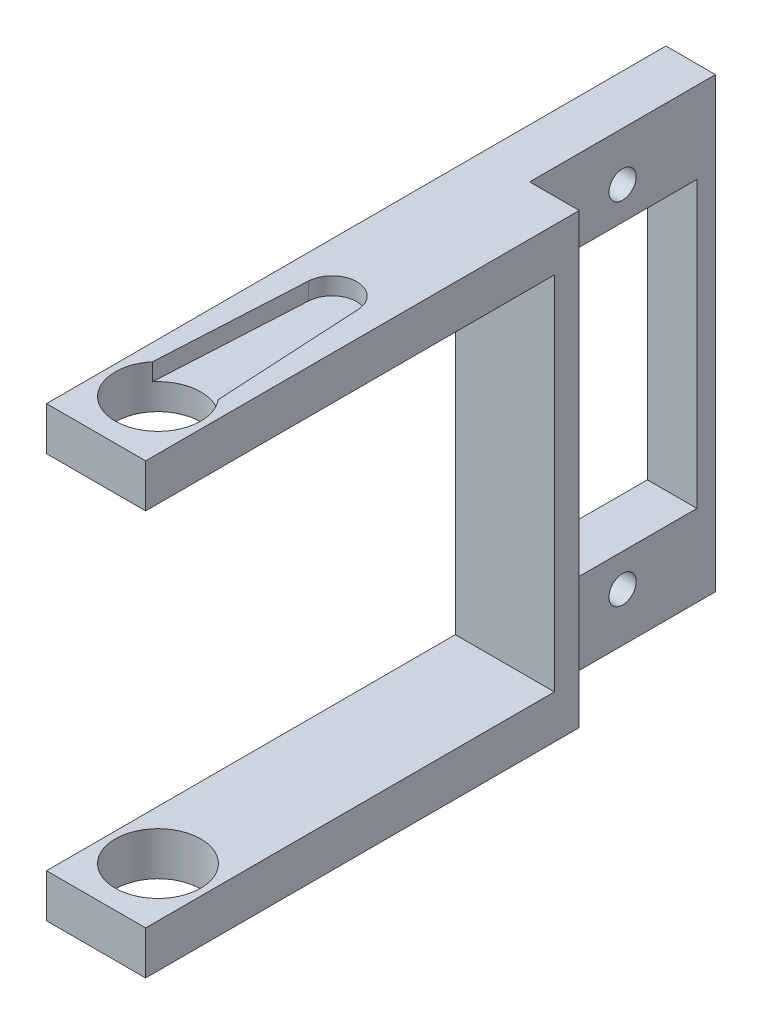
SolidWorks part; units mm, degrees
ref_plane "Front Plane" through (0, 0, 0) normal (0, 0, 1) x (1, 0, 0)
ref_plane "Top Plane" through (0, 0, 0) normal (0, 1, 0) x (1, 0, 0)
ref_plane "Right Plane" through (0, 0, 0) normal (1, 0, 0) x (0, 0, -1)
sketch "Sketch2" plane through (0, 0, 0) normal (0, 0, 1) x (1, 0, 0)
  line L1 (-8.6815, 1.0365) -> (-0.6815, 1.0365)
  line L2 (-8.6815, 1.0365) -> (-8.6815, -35.1135)
  line L3 (-8.6815, -35.1135) -> (-0.6815, -35.1135)
  line L4 (-0.6815, 1.0365) -> (-0.6815, -35.1135)
  line L13 (-8.6815, 1.0365) -> (-0.6815, 1.0365)
  line L14 (-8.6815, 1.0365) -> (-8.6815, -2.4635)
  line L15 (-8.6815, -2.4635) -> (-0.6815, -2.4635)
  line L16 (-0.6815, 1.0365) -> (-0.6815, -2.4635)
  line L21 (-8.6815, -35.1135) -> (-0.6815, -35.1135)
  line L22 (-8.6815, -35.1135) -> (-8.6815, -31.6135)
  line L23 (-8.6815, -31.6135) -> (-0.6815, -31.6135)
  line L24 (-0.6815, -35.1135) -> (-0.6815, -31.6135)
  dimension "D1" = 8
  dimension "D2" = 36.15
  dimension "D3" = 3.5
  dimension "D4" = 3.5
extrude "Boss-Extrude2" add sketch "Sketch2" along normal blind 35 contours L2 L15 L4 L1 | L22 L21 L24 L23 region at (-4.6815, -0.7135, 0)
extrude "Boss-Extrude3" add sketch "Sketch2<3>" along normal blind 2 contours L15 L2 L3 L4 region at (-4.6815, -17.0385, 0)
sketch "Sketch2<3>" plane through (0, 0, 0) normal (0, 0, 1) x (1, 0, 0) same geometry as "Sketch2"
sketch "Sketch7" plane through (0, 0, 0) normal (0, 0, -1) x (-1, 0, 0)
  line L5 (8.6815, -35.1135) -> (0.6815, -35.1135) construction
  line L6 (8.6815, 1.0365) -> (4.6815, 1.0365)
  line L7 (8.6815, 1.0365) -> (8.6815, -35.1135)
  line L8 (8.6815, -35.1135) -> (4.6815, -35.1135)
  line L9 (4.6815, 1.0365) -> (4.6815, -35.1135)
extrude "Boss-Extrude4" add sketch "Sketch7" along normal blind 15
sketch "Sketch8" plane through (-4.6815, 0, 0) normal (1, 0, 0) x (0, 0, -1)
  line L0 (7.5, -5.5385) -> (7.5, 1.0365) construction
  line L1 (1.5, -5.5385) -> (13.5, -5.5385)
  line L2 (1.5, -5.5385) -> (1.5, -28.5385)
  line L3 (1.5, -28.5385) -> (13.5, -28.5385)
  line L4 (13.5, -5.5385) -> (13.5, -28.5385)
  line L5 (15, 1.0365) -> (0, 1.0365) construction
  line L6 (13.5, -17.0385) -> (15, -17.0385) construction
  line L7 (15, 1.0365) -> (15, -35.1135) construction
  circle A2 centre (7.5, -2.8885) radius 1.1
  circle A3 centre (7.5, -31.1885) radius 1.1
  dimension "D3" = 2.2
  dimension "D1" = 23
  dimension "D2" = 12
  dimension "D4" = 2.65
  dimension "D5" = 2.65
extrude "Cut-Extrude5" cut sketch "Sketch8" against normal up to next
sketch "Sketch9" plane through (0, 1.0365, 0) normal (0, 1, 0) x (1, 0, 0)
  line L0 (-2.6845, -15.8409) -> (-2.0315, -27.7909)
  line L1 (-7.3315, -27.7909) -> (-6.6786, -15.8409)
  line L2 (-8.6815, -35) -> (-0.6815, -35) construction
  line L3 (-4.6815, -30) -> (-4.6815, -35) construction
  arc A0 (-7.3315, -27.7909) -> (-2.0315, -27.7909) centre (-4.6815, -30) ccw
  arc A1 (-2.6845, -15.8409) -> (-6.6786, -15.8409) centre (-4.6815, -15.95) ccw
  point P4 (-7.0051, -21.8159)
  dimension "D1" = 3.45
  dimension "D5" = 2
  dimension "D2" = 5
  dimension "D3" = 11.95
  dimension "D4" = 11.95
  dimension "D6" = 5.3
extrude "Cut-Extrude6" cut sketch "Sketch9" against normal blind 1.4
sketch "Sketch10" plane through (0, 1.0365, 0) normal (0, 1, 0) x (1, 0, 0)
  circle A0 centre (-4.6815, -30) radius 3.45
  dimension "D1" = 6.9
extrude "Cut-Extrude7" cut sketch "Sketch10" against normal through all
